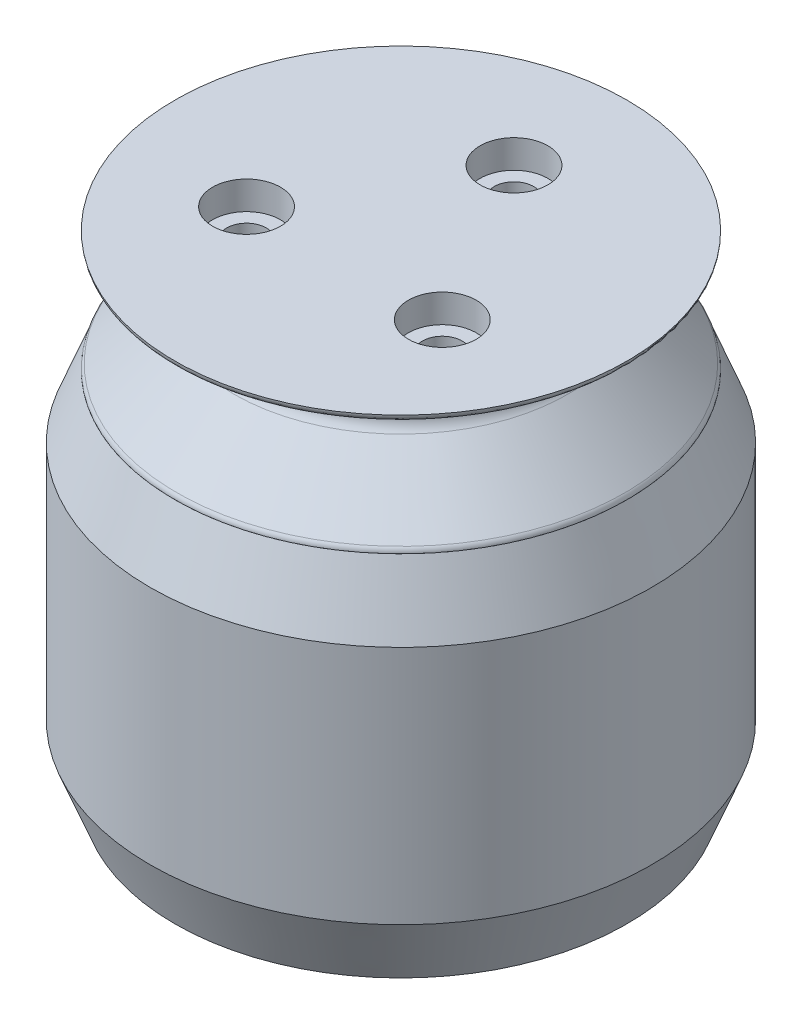
SolidWorks part; units mm, degrees
ref_plane "Front Plane" through (0, 0, 0) normal (0, 0, 1) x (1, 0, 0)
ref_plane "Top Plane" through (0, 0, 0) normal (0, 1, 0) x (1, 0, 0)
ref_plane "Right Plane" through (0, 0, 0) normal (1, 0, 0) x (0, 0, -1)
sketch "Sketch1" plane through (0, 0, 0) normal (1, 0, 0) x (0, 0, -1)
  line L0 (0, 0) -> (16, 0)
  line L1 (16, 0) -> (17.75, 4.5)
  line L2 (17.75, 4.5) -> (17.75, 21.5)
  line L3 (17.75, 21.5) -> (16, 26)
  line L4 (16, 26) -> (5.5, 26)
  line L5 (5.5, 26) -> (5.5, 30)
  line L6 (5.5, 30) -> (0, 30)
  line L7 (0, 30) -> (0, 0)
  point P9 (14.4399, 0)
  point P10 (0, 0)
  point P11 (16, 18.9137)
  dimension "D1" = 30
  dimension "D2" = 17.75
  dimension "D3" = 16
  dimension "D4" = 4.5
  dimension "D5" = 26
  dimension "D6" = 5.5
revolve "Revolve1" add sketch "Sketch1" angle 360 about L7
sketch "Sketch2" plane through (0, 0, 0) normal (1, 0, 0) x (0, 0, -1)
  line L0 (-16, 26) -> (-6, 26)
  line L1 (16, 26) -> (-16, 26) construction
  line L2 (-6, 26) -> (-6, 30.5)
  line L3 (-6, 30.5) -> (0, 30.5)
  line L4 (0, 30.5) -> (0, 34.5)
  line L5 (0, 34.5) -> (-16, 34.5)
  line L6 (-15.7113, 34.0468) -> (-12.1795, 32.4)
  line L7 (-11.8239, 30.3832) -> (-15.8536, 26.3536)
  line L8 (5.5, 30) -> (-5.5, 30) construction
  line L9 (-5.5, 30) -> (-5.5, 26) construction
  arc A0 (-16, 34.5) -> (-15.7113, 34.0468) centre (-15.5, 34.5) ccw
  arc A1 (-12.1795, 32.4) -> (-11.8239, 30.3832) centre (-12.7078, 31.2671) cw
  arc A2 (-15.8536, 26.3536) -> (-16, 26) centre (-15.5, 26) ccw
  point P17 (0, 0)
  point P18 (0, 0)
  point P19 (-13.3875, 30.1067)
  point P24 (-13.7951, 31.0637)
  dimension "D1" = 0.5
  dimension "D6" = 1.25
  dimension "D2" = 25
  dimension "D3" = 0.5
  dimension "D4" = 0.5
  dimension "D5" = 45
  dimension "D7" = 8.5
revolve "Revolve2" add sketch "Sketch2" angle 360 about L4
sketch "Sketch3" plane through (0, 34.5, 0) normal (0, 1, 0) x (1, 0, 0)
  circle A0 centre (0, 8) radius 1.4
  circle A1 centre (6.9282, -4) radius 1.4
  circle A2 centre (-6.9282, -4) radius 1.4
  point P4 (0, 0)
  point P9 (0, 0)
  dimension "D1" = 2.8
  dimension "D2" = 3
  dimension "D3" = 8
extrude "Cut-Extrude1" cut sketch "Sketch3" against normal blind 10
extrude "Cut-Extrude-Thin1" cut sketch "Sketch3<2>" against normal blind 2 thin thin type one direction wall 1
sketch "Sketch3<2>" plane through (0, 34.5, 0) normal (0, 1, 0) x (1, 0, 0) same geometry as "Sketch3"
